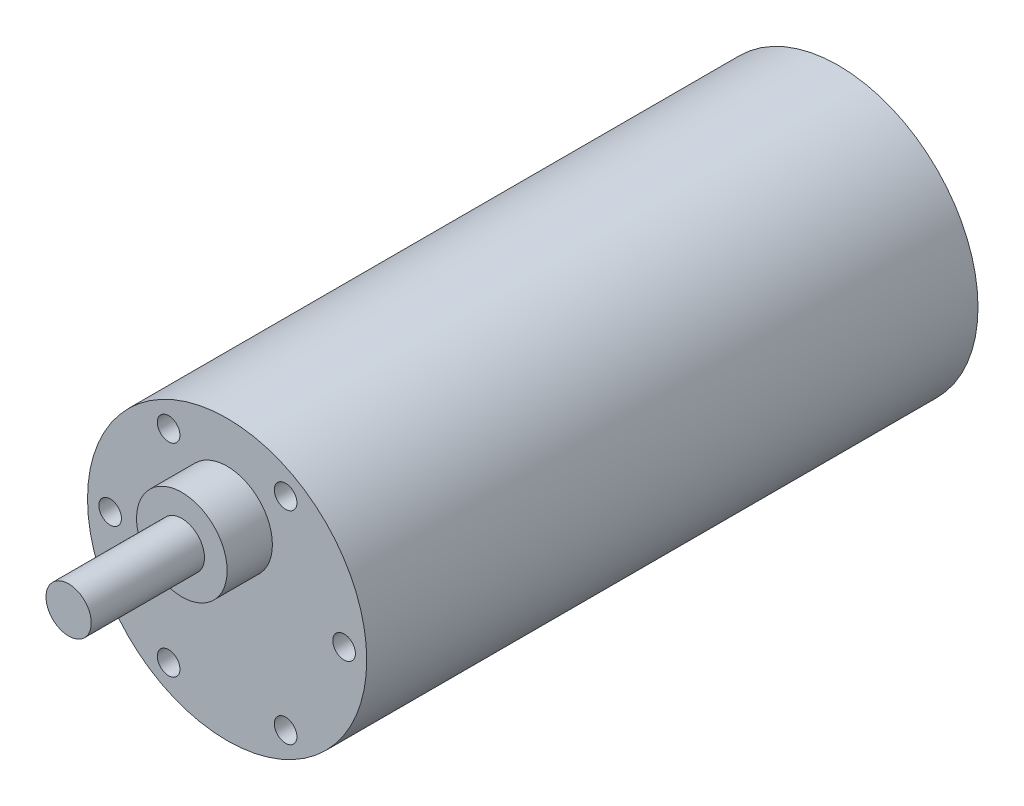
SolidWorks part; units mm, degrees
ref_plane "Front Plane" through (0, 0, 0) normal (0, 0, 1) x (1, 0, 0)
ref_plane "Top Plane" through (0, 0, 0) normal (0, 1, 0) x (1, 0, 0)
ref_plane "Right Plane" through (0, 0, 0) normal (1, 0, 0) x (0, 0, -1)
sketch "Sketch1" plane through (0, 0, 0) normal (0, 0, 1) x (1, 0, 0)
  circle A0 centre (0, 0) radius 18.5
  dimension "D1" = 37
extrude "Boss-Extrude1" add sketch "Sketch1" against normal blind 57 and the other way blind 24
sketch "Sketch2" plane through (0, 0, 24) normal (0, 0, 1) x (1, 0, 0)
  line L0 (0, 0) -> (15.5, 0) construction
  circle A0 centre (15.5, 0) radius 1.5
  circle A1 centre (7.75, -13.4234) radius 1.5
  circle A2 centre (-7.75, -13.4234) radius 1.5
  circle A3 centre (-15.5, 0) radius 1.5
  circle A4 centre (-7.75, 13.4234) radius 1.5
  circle A5 centre (7.75, 13.4234) radius 1.5
  dimension "D1" = 15.5
  dimension "D2" = 3
  dimension "D3" = 6
extrude "Cut-Extrude1" cut sketch "Sketch2" against normal blind 5
sketch "Sketch3" plane through (0, 0, 24) normal (0, 0, 1) x (1, 0, 0)
  line L0 (0, 0) -> (0, 7) construction
  circle A0 centre (0, 7) radius 6
  circle A1 centre (0, 7) radius 3
  dimension "D2" = 12
  dimension "D3" = 6
  dimension "D1" = 7
extrude "Boss-Extrude2" add sketch "Sketch3" along normal blind 6
extrude "Boss-Extrude3" add sketch "Sketch3<2>" along normal blind 21 contours A1
sketch "Sketch3<2>" plane through (0, 0, 24) normal (0, 0, 1) x (1, 0, 0) same geometry as "Sketch3"
